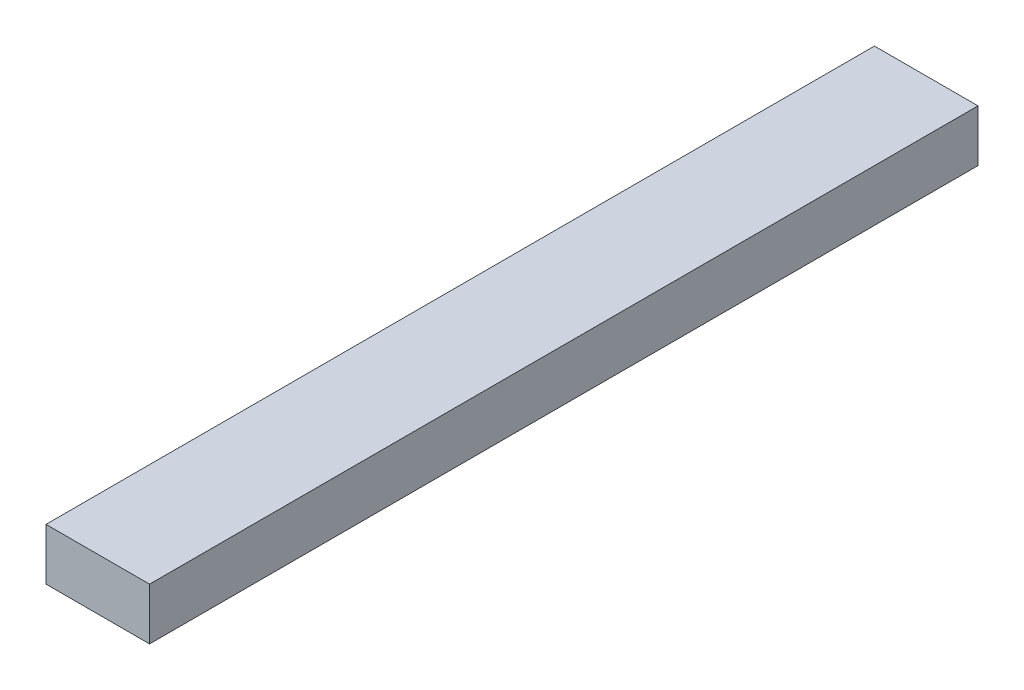
SolidWorks part; units mm, degrees
material "Alumina"
ref_plane "Front Plane" through (0, 0, 0) normal (0, 0, 1) x (1, 0, 0)
ref_plane "Top Plane" through (0, 0, 0) normal (0, 1, 0) x (1, 0, 0)
ref_plane "Right Plane" through (0, 0, 0) normal (1, 0, 0) x (0, 0, -1)
sketch "Sketch1" plane through (0, 0, 0) normal (0, 0, 1) x (1, 0, 0)
  line L1 (-12.7, 6.35) -> (12.7, 6.35)
  line L2 (-12.7, 6.35) -> (-12.7, -6.35)
  line L3 (-12.7, -6.35) -> (12.7, -6.35)
  line L4 (12.7, 6.35) -> (12.7, -6.35)
  point P4 (-12.7, 0)
  point P6 (0, 6.35)
  dimension "D1" = 12.7
  dimension "D2" = 25.4
extrude "Boss-Extrude1" add sketch "Sketch1" along normal blind 203.2
sketch "Sketch4" plane through (0, 0, 0) normal (0, 0, -1) x (-1, 0, 0)
  line L0 (-12.7, -6.35) -> (-12.7, 6.35) construction
  line L1 (-11.43, 5.08) -> (11.43, 5.08)
  line L2 (-11.43, 5.08) -> (-11.43, -5.08)
  line L3 (-11.43, -5.08) -> (11.43, -5.08)
  line L4 (11.43, 5.08) -> (11.43, -5.08)
  line L5 (-12.7, 6.35) -> (12.7, 6.35) construction
  line L6 (12.7, -6.35) -> (-12.7, -6.35) construction
  line L7 (12.7, 6.35) -> (12.7, -6.35) construction
  dimension "D1" = 1.27
  dimension "D2" = 1.27
  dimension "D3" = 1.27
  dimension "D4" = 1.27
extrude "Cut-Extrude1" cut sketch "Sketch4" against normal blind 107.95
